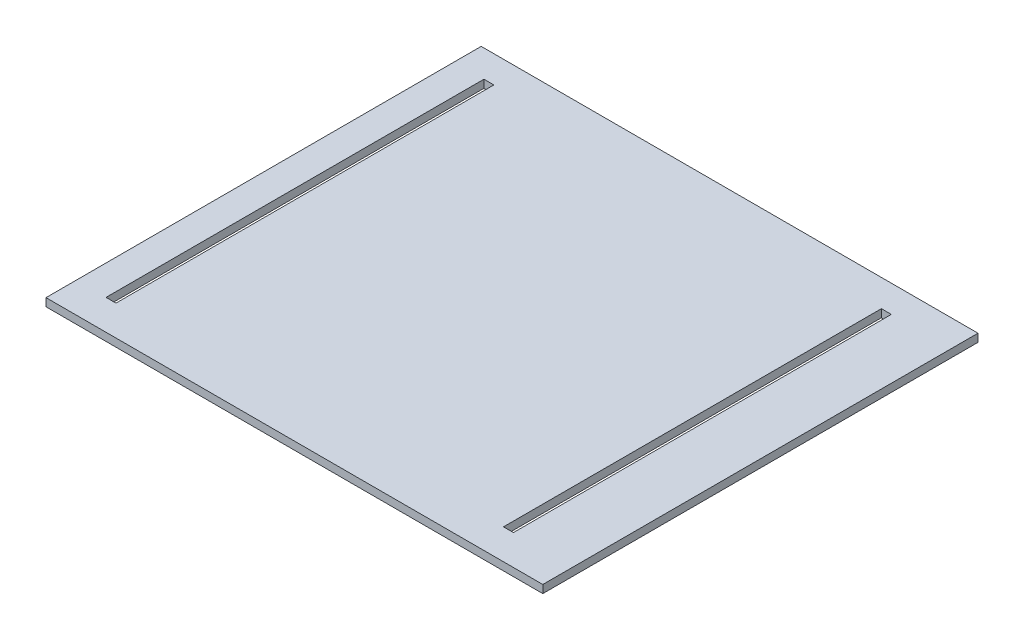
SolidWorks part; units mm, degrees
ref_plane "Front Plane" through (0, 0, 0) normal (0, 0, 1) x (1, 0, 0)
ref_plane "Top Plane" through (0, 0, 0) normal (0, 1, 0) x (1, 0, 0)
ref_plane "Right Plane" through (0, 0, 0) normal (1, 0, 0) x (0, 0, -1)
sketch "Sketch1" plane through (0, 0, 0) normal (0, 1, 0) x (1, 0, 0)
  line L0 (-110, 95.8859) -> (-110, -94.2851)
  line L1 (-125, -109.5) -> (125, -109.5)
  line L2 (-125, -109.5) -> (-125, 109.5)
  line L3 (-125, 109.5) -> (125, 109.5)
  line L4 (125, -109.5) -> (125, 109.5)
  line L5 (-125, -109.5) -> (125, 109.5) construction
  line L6 (-125, 109.5) -> (125, -109.5) construction
  line L7 (-110, -94.2851) -> (-105, -94.2851)
  line L8 (-105, -94.2851) -> (-105, 95.8859)
  line L9 (-105, 95.8859) -> (-110, 95.8859)
  line L10 (90, 95.8859) -> (90, -94.2851)
  line L11 (90, -94.2851) -> (95, -94.2851)
  line L12 (95, -94.2851) -> (95, 95.8859)
  line L13 (95, 95.8859) -> (90, 95.8859)
  point P0 (0, 0)
  dimension "D1" = 219
  dimension "D2" = 250
  dimension "D3" = 5
  dimension "D4" = 5
  dimension "D5" = 30
  dimension "D6" = 15
extrude "Boss-Extrude1" add sketch "Sketch1" along normal blind 4
